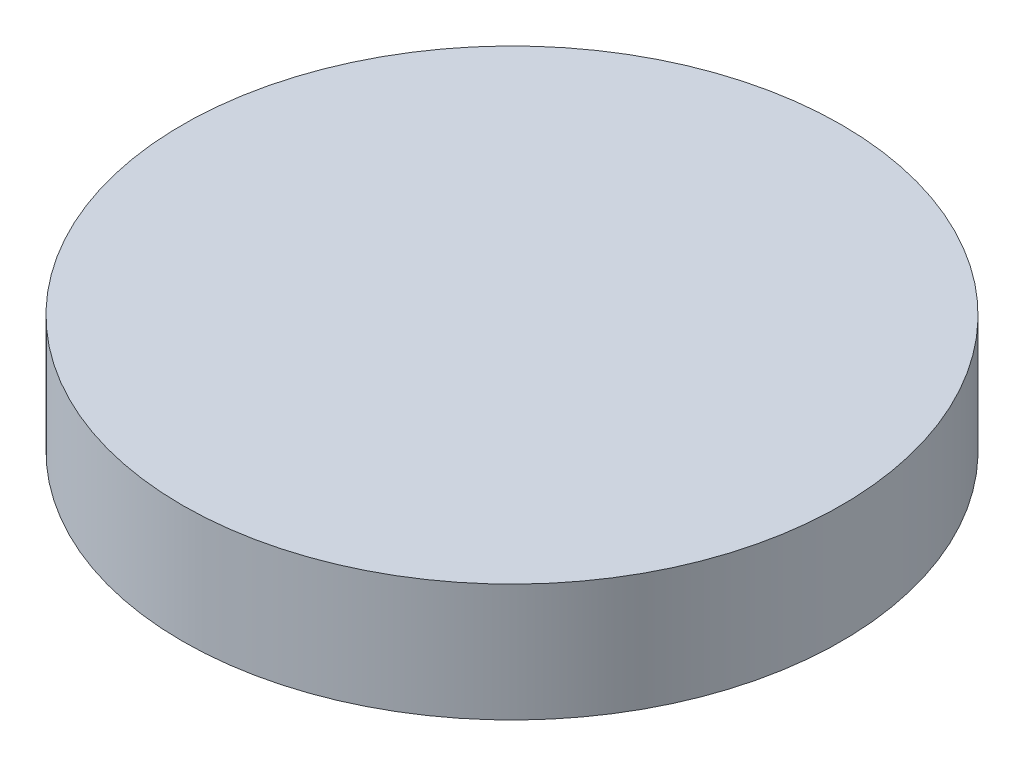
SolidWorks part; units mm, degrees
ref_plane "Front Plane" through (0, 0, 0) normal (0, 0, 1) x (1, 0, 0)
ref_plane "Top Plane" through (0, 0, 0) normal (0, 1, 0) x (1, 0, 0)
ref_plane "Right Plane" through (0, 0, 0) normal (1, 0, 0) x (0, 0, -1)
sketch "Sketch2" plane through (0, 53, 0) normal (0, 1, 0) x (1, 0, 0)
  circle A0 centre (-27.25, 13.5) radius 7
  circle A1 centre (-27.25, 13.5) radius 7.5 construction
  dimension "D1" = 0.5
extrude "Boss-Extrude1" add sketch "Sketch2" against normal offset from surface (2.5 mm away) 0.5
